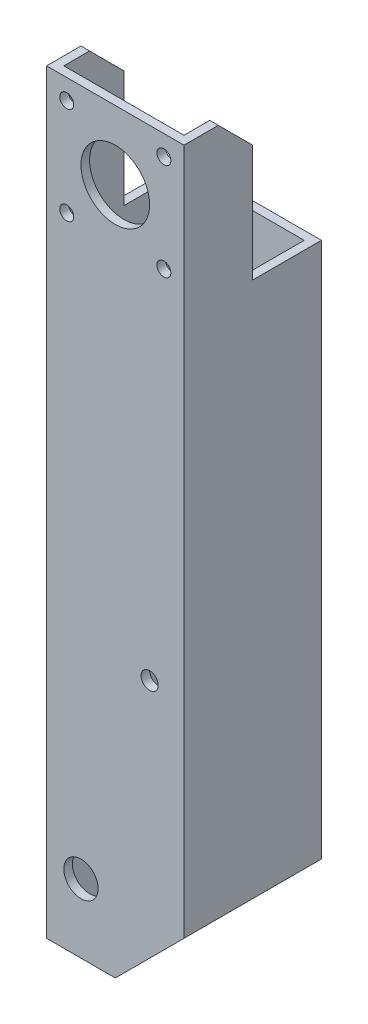
SolidWorks part; units mm, degrees
ref_plane "Front Plane" through (0, 0, 0) normal (0, 0, 1) x (1, 0, 0)
ref_plane "Top Plane" through (0, 0, 0) normal (0, 1, 0) x (1, 0, 0)
ref_plane "Right Plane" through (0, 0, 0) normal (1, 0, 0) x (0, 0, -1)
sketch "Sketch1" plane through (0, 0, 0) normal (0, 1, 0) x (1, 0, 0)
  line L0 (47.625, 3.175) -> (47.625, 47.625)
  line L1 (0, 0) -> (50.8, 0)
  line L2 (0, 0) -> (0, 50.8)
  line L3 (0, 50.8) -> (50.8, 50.8)
  line L4 (50.8, 0) -> (50.8, 50.8)
  line L5 (3.175, 47.625) -> (47.625, 47.625)
  line L6 (3.175, 3.175) -> (3.175, 47.625)
  line L7 (3.175, 3.175) -> (47.625, 3.175)
  dimension "D1" = 50.8
  dimension "D2" = 50.8
  dimension "D3" = 3.175
extrude "Boss-Extrude1" add sketch "Sketch1" along normal blind 279.4
sketch "Sketch2" plane through (0, 0, -50.8) normal (0, 0, -1) x (-1, 0, 0)
  line L1 (27.94, 0) -> (-27.94, 0) construction
  line L2 (-50.8, 279.4) -> (-50.8, 0) construction
  line L3 (-50.8, 279.4) -> (0, 279.4) construction
  line L4 (0, 279.4) -> (0, 0) construction
  circle A0 centre (-12.7, 25.4) radius 6.35
  circle A1 centre (-25.4, 254) radius 12.7
  dimension "D1" = 25.4
  dimension "D2" = 12.7
  dimension "D3" = 25.4
  dimension "D4" = 38.1
  dimension "D5" = 25.4
  dimension "D6" = 25.4
extrude "Cut-Extrude1" cut sketch "Sketch2" against normal through all
chamfer "Chamfer1" distance 25.4 angle 45 1 edges at (50.8, 0, -25.4)
sketch "Sketch3" plane through (0, 0, -50.8) normal (0, 0, -1) x (-1, 0, 0)
  circle A0 centre (-38.1, 101.6) radius 3.175
  circle A1 centre (-12.7, 25.4) radius 6.35 construction
  dimension "D1" = 25.4
  dimension "D2" = 6.35
  dimension "D3" = 76.2
extrude "Cut-Extrude2" cut sketch "Sketch3" against normal through all
sketch "Sketch4" plane through (0, 0, 0) normal (-1, 0, 0) x (0, 0, 1)
  line L1 (-50.8, 279.4) -> (-25.4, 279.4)
  line L2 (-50.8, 279.4) -> (-50.8, 223.52)
  line L3 (-50.8, 223.52) -> (-25.4, 223.52)
  line L4 (-25.4, 279.4) -> (-25.4, 223.52)
  point P5 (-25.4, 251.46)
  dimension "D1" = 25.4
  dimension "D2" = 55.88
extrude "Cut-Extrude3" cut sketch "Sketch4" against normal through all
chamfer "Chamfer2" distance 12.7 angle 45 2 edges at (49.2125, 279.4, -25.4) (1.5875, 279.4, -25.4)
sketch "Sketch6" plane through (0, 0, 0) normal (0, 0, 1) x (1, 0, 0)
  circle A0 centre (7.4395, 271.9605) radius 2.5797
  circle A1 centre (7.4395, 236.0395) radius 2.5797
  circle A2 centre (43.3605, 236.0395) radius 2.5797
  circle A3 centre (43.3605, 271.9605) radius 2.5797
  dimension "D1" = 5.1594
extrude "Cut-Extrude5" cut sketch "Sketch6" against normal up to next
move or copy body "Body-Move/Copy1" [suppressed] bodies to move or copy 104
